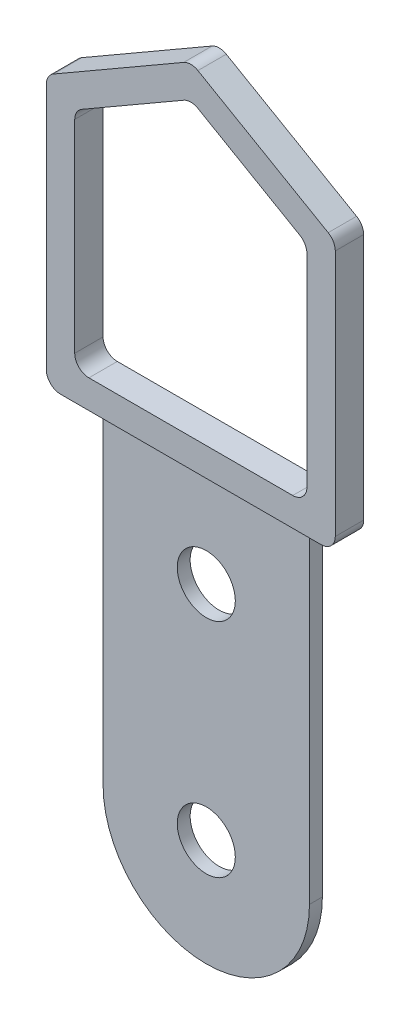
SolidWorks part; units mm, degrees
material "AISI 304"
ref_plane "前基準面" through (0, 0, 0) normal (0, 0, 1) x (1, 0, 0)
ref_plane "上基準面" through (0, 0, 0) normal (0, 1, 0) x (1, 0, 0)
ref_plane "右基準面" through (0, 0, 0) normal (1, 0, 0) x (0, 0, -1)
sketch "草圖2" plane through (0, 0, 0) normal (0, 0, 1) x (1, 0, 0)
  line L0 (-15.0569, 43) -> (20.4221, 43) construction
  line L1 (-8, 18) -> (8, 18)
  line L2 (-8, 15.8) -> (-8, -18)
  line L3 (-8, -18) -> (8, -18)
  line L4 (8, 18) -> (8, -18)
  line L5 (-8, 18) -> (8, -18) construction
  line L6 (-8, -18) -> (8, 18) construction
  line L7 (0, -33.55) -> (0, 33.55) construction
  line L8 (-0.55, 42.8526) -> (-11.2, 36.7038)
  line L9 (0, 40.6298) -> (-9, 35.4337)
  line L10 (-8, 18) -> (-9, 18)
  line L11 (-8, 15.8) -> (-11.2, 15.8)
  line L12 (-9, 35.4337) -> (-9, 18)
  line L13 (-11.2, 36.7038) -> (-11.2, 15.8)
  line L14 (-9, 39.8885) -> (-9, 13.9721) construction
  line L15 (-11.2, 39.8885) -> (-11.2, 13.9721) construction
  line L16 (0, 40.6298) -> (9, 35.4337)
  line L17 (0.55, 40.9474) -> (-10.1, 34.7986) construction
  line L18 (-8, 18) -> (-23.6749, 18) construction
  line L19 (-8, 15.8) -> (-23.6749, 15.8) construction
  line L20 (8, 18) -> (9, 18)
  line L21 (8, 15.8) -> (11.2, 15.8)
  line L22 (9, 35.4337) -> (9, 18)
  line L23 (11.2, 36.7038) -> (11.2, 15.8)
  line L24 (-0.55, 40.9474) -> (10.1, 34.7986) construction
  line L25 (0.55, 42.8526) -> (11.2, 36.7038)
  arc A0 (0.55, 42.8526) -> (-0.55, 42.8526) centre (0, 41.9) ccw
  point P0 (0, 0)
  dimension "D4" = 2.2
  dimension "D1" = 36
  dimension "D2" = 16
  dimension "D3" = 25
  dimension "D5" = 30
  dimension "D8" = 9
  dimension "D6" = 2.2
  dimension "D7" = 2.2
  dimension "D9" = 2.2
extrude "填料-伸長1" add sketch "草圖2" along normal blind 2.2 contours L25 A0 L8 L13 L11 L2 L3 L4 L1 L10 L12 L9 L16 L22 L20 L21 L23 region at (0, 6.086, 0)
sketch "草圖4" plane through (0, 0, 2.2) normal (0, 0, 1) x (1, 0, 0)
  line L0 (-8, 15.8) -> (8, 15.8)
  line L9 (8, -18) -> (8, 15.8)
  line L10 (8, 15.8) -> (11.2, 15.8)
  line L11 (11.2, 15.8) -> (11.2, 36.7038)
  line L12 (11.2, 36.7038) -> (0.55, 42.8526)
  line L13 (-0.55, 42.8526) -> (-11.2, 36.7038)
  line L14 (-11.2, 36.7038) -> (-11.2, 15.8)
  line L15 (-11.2, 15.8) -> (-8, 15.8)
  line L16 (-8, 15.8) -> (-8, -18)
  line L17 (-8, -18) -> (8, -18)
  line L18 (8, -18) -> (8, 15.8)
  line L19 (8, 15.8) -> (11.2, 15.8)
  line L20 (11.2, 15.8) -> (11.2, 36.7038)
  line L21 (11.2, 36.7038) -> (0.55, 42.8526)
  line L22 (-0.55, 42.8526) -> (-11.2, 36.7038)
  line L23 (-11.2, 36.7038) -> (-11.2, 15.8)
  line L24 (-11.2, 15.8) -> (-8, 15.8)
  line L25 (-8, 15.8) -> (-8, -18)
  line L26 (-8, -18) -> (8, -18)
  arc A1 (0.55, 42.8526) -> (-0.55, 42.8526) centre (0, 41.9) ccw
  arc A2 (0.55, 42.8526) -> (-0.55, 42.8526) centre (0, 41.9) ccw
  line M11 (8, -18) -> (8, 15.8)
  line M19 (-8, 15.8) -> (-8, -18)
  line M20 (-8, -18) -> (8, -18)
  dimension "D1" = 0
extrude "除料-伸長1" cut sketch "草圖4" against normal blind 1.2 contours L0 M19 M20 M11 region at (0, -1.1, 2.2)
sketch "草圖5" plane through (0, 0, 1) normal (0, 0, 1) x (1, 0, 0)
  line L0 (0, -1.21) -> (0, 1.21) construction
  line L4 (8, 15.8) -> (-8, 15.8)
  line L5 (-8, 15.8) -> (-8, -18)
  line L6 (-8, -18) -> (8, -18)
  line L7 (8, -18) -> (8, 15.8)
  line L8 (8, 15.8) -> (-8, 15.8)
  line L9 (-8, 15.8) -> (-8, -18)
  line L10 (-8, -18) -> (8, -18)
  line L11 (8, -18) -> (8, 15.8)
  point P2 (0, 7.5)
  point P4 (0, -9.7)
  dimension "D2" = 33.8
  dimension "D3" = 8.3
  dimension "D4" = 8.3
  dimension "D1" = 0
hole_wizard "Ø2.0mm 定位孔1" positions "3D草圖1" profile "草圖6" hole size "Ø2.0" standard "Ansi Metric" end condition through all
sketch3d "3D草圖1"
  point P0 (0, 7.5, 1)
  point P3 (0, -9.7, 1)
sketch "草圖6" plane through (0, 7.5, 1) normal (1, 0, 0) x (0, -1, 0)
  line L0 (0, 0) -> (0, 1)
  line L1 (0, 1) -> (2.25, 1)
  line L2 (2.25, 1) -> (2.25, 0)
  line L5 (2.25, 0) -> (0, 0)
  line L11 (0, -6.35) -> (0, 107.95) construction
  dimension "貫穿孔直徑" = 4.5
  dimension "貫穿孔深度" = 1
fillet "圓角1" radius 1.1 9 edges at (-11.2, 15.8, 1.1) (11.2, 15.8, 1.1) (9, 18, 1.1) (-9, 18, 1.1) (11.2, 36.7038, 1.1) (9, 35.4337, 1.1) (-11.2, 36.7038, 1.1) (-9, 35.4337, 1.1) (0, 40.6298, 1.1)
fillet "圓角2" radius 8 2 edges at (8, -18, 0.5) (-8, -18, 0.5)
fillet "圓角3" radius 1 2 edges at (8, 15.8, 0.5) (-8, 15.8, 0.5)
